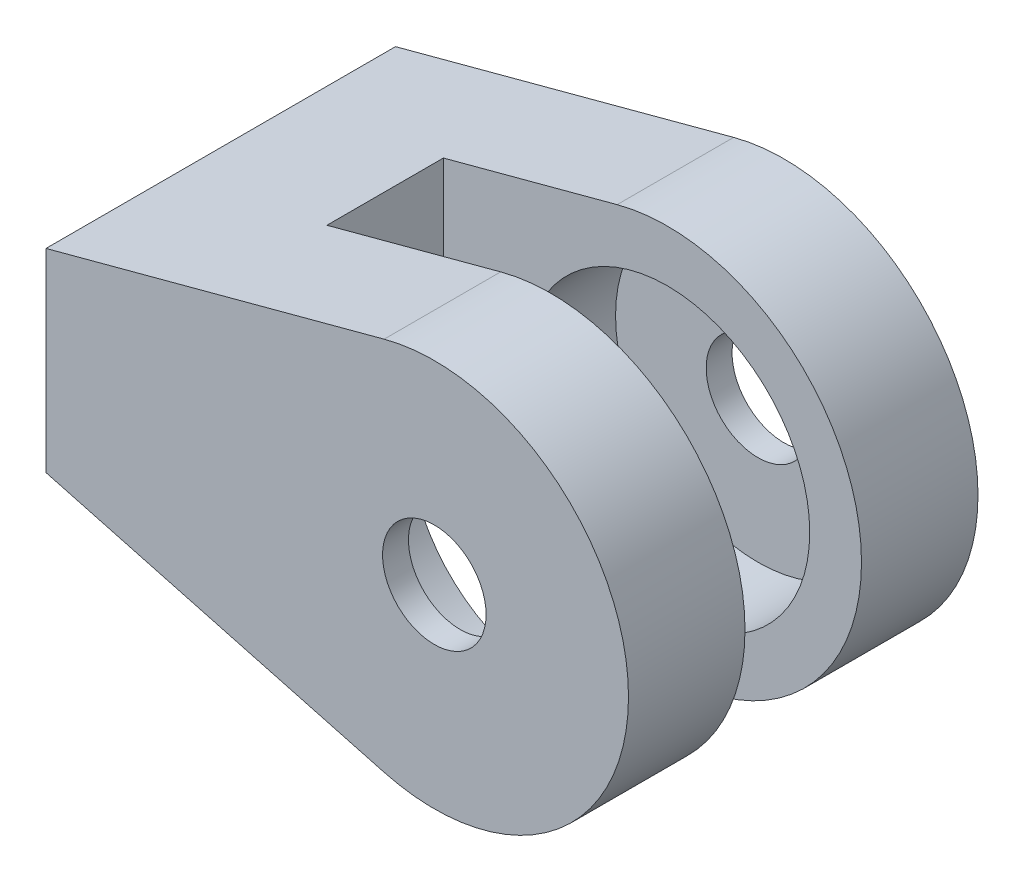
SolidWorks part; units mm, degrees
ref_plane "Front Plane" through (0, 0, 0) normal (0, 0, 1) x (1, 0, 0)
ref_plane "Top Plane" through (0, 0, 0) normal (0, 1, 0) x (1, 0, 0)
ref_plane "Right Plane" through (0, 0, 0) normal (1, 0, 0) x (0, 0, -1)
sketch "Sketch1" plane through (0, 0, 0) normal (0, 0, 1) x (1, 0, 0)
  line L0 (-3.8775, 14.4902) -> (-30, 7.5)
  line L3 (-30, 7.5) -> (-30, -7.5)
  line L4 (-30, -7.5) -> (-3.8775, -14.4902)
  circle A2 centre (0, 0) radius 11 construction
  circle A3 centre (0, 0) radius 15
  point P4 (0, 0)
  point P7 (0, 0)
  point P10 (-37.6389, 7.2524)
  point P11 (-30.3339, 7.5)
  dimension "D1" = 30
  dimension "D3" = 22
  dimension "D2" = 15
  dimension "D4" = 30
extrude "Boss-Extrude1" add sketch "Sketch1" along normal blind 9 contours A3 L0 L3 L4 | A3 region at (-20.555, 0, 0) region at (0, 0, 0)
sketch "Sketch2" plane through (0, 0, 9) normal (0, 0, 1) x (1, 0, 0)
  circle A0 centre (0, 0) radius 11
  dimension "D1" = 22
extrude "Cut-Extrude1" cut sketch "Sketch2" against normal offset from surface (7 mm away) 2 up to face at (-12.2194, 0, 0)
sketch "Sketch3" plane through (0, 0, 2) normal (0, 0, 1) x (1, 0, 0)
  circle A0 centre (0, 0) radius 4
  dimension "D1" = 8
extrude "Cut-Extrude2" cut sketch "Sketch3" against normal up to next contours A0
sketch "Sketch4" plane through (0, 0, 9) normal (0, 0, 1) x (1, 0, 0)
  line L0 (-30, -7.5) -> (-3.8775, -14.4902) construction
  line L1 (-3.8775, 14.4902) -> (-30, 7.5) construction
  line L2 (-30, 7.5) -> (-30, -7.5) construction
  line L3 (-30, -7.5) -> (-3.8775, -14.4902)
  line L4 (-3.8775, 14.4902) -> (-30, 7.5)
  line L5 (-30, 7.5) -> (-30, -7.5)
  line L6 (-17.3, 10.8984) -> (-17.3, -10.8984)
  dimension "D1" = 12.7
ref_plane "Plane2" through (0, 0, 13.5) normal (0, 0, 1) x (1, 0, 0)
mirror "Mirror8" about plane through (0, 0, 13.5) normal (0, 0, 1) of bodies 103
extrude "Boss-Extrude3" add sketch "Sketch4" along normal up to next contours L6 L4 L5 L3
sketch "Sketch6" plane through (-30, 0, 0) normal (-1, 0, 0) x (0, 0, 1)
  line L1 (13.5, -16.5) -> (13.5, 16.5) construction
  circle A0 centre (13.5, 0) radius 5
  circle A1 centre (13.5, 0) radius 4
  circle A2 centre (13.5, 0) radius 6.5
  point P0 (0, 0)
  point P2 (-13.4201, 0)
  dimension "D1" = 10
  dimension "D2" = 1
  dimension "D3" = 1.5
extrude "Cut-Extrude3" cut sketch "Sketch6" against normal blind 11.43 contours A0 A1 | A1 | A1 | A0 A1 region at (-30, 0, 8.6414) region at (-30, 0, 13.5)
